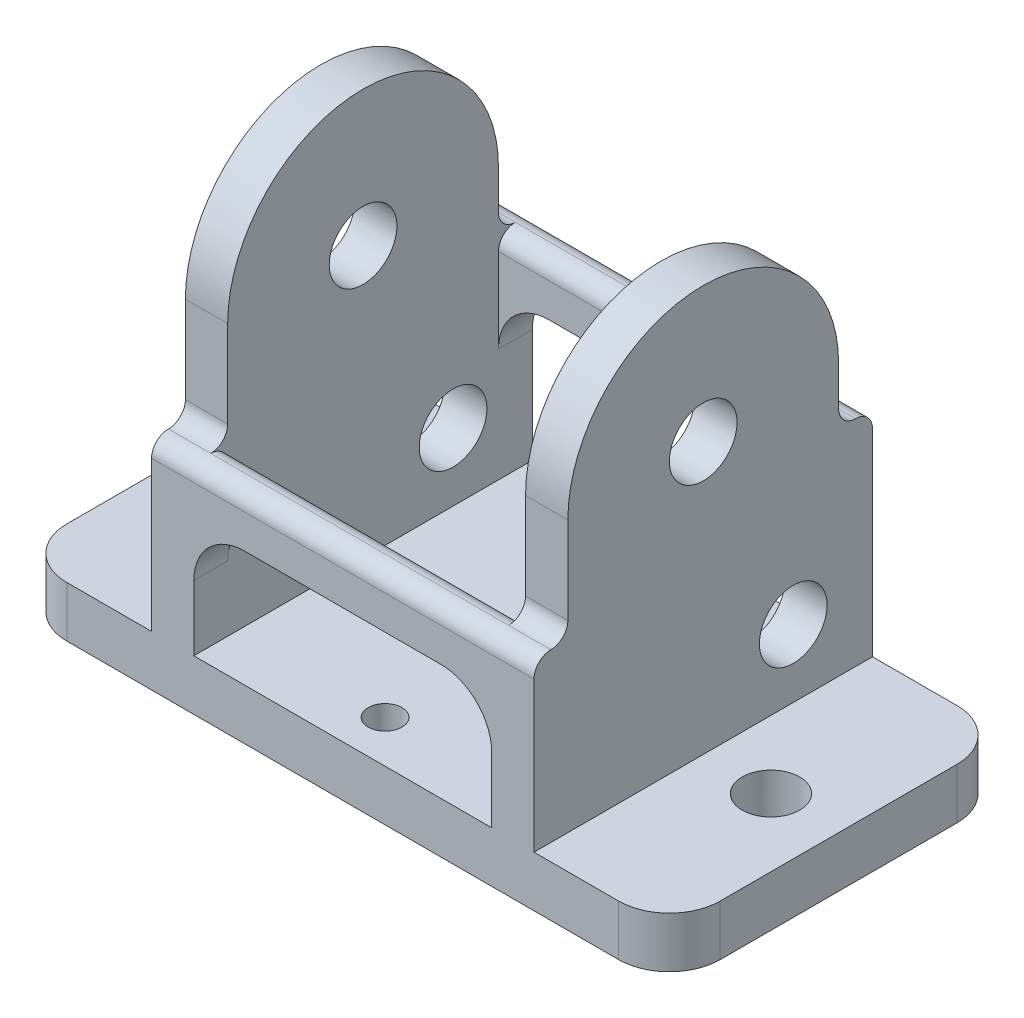
SolidWorks part; units mm, degrees
ref_plane "Plan de face" through (0, 0, 0) normal (0, 0, 1) x (1, 0, 0)
ref_plane "Plan de dessus" through (0, 0, 0) normal (0, 1, 0) x (1, 0, 0)
ref_plane "Plan de droite" through (0, 0, 0) normal (1, 0, 0) x (0, 0, -1)
sketch "Esquisse2" plane through (0, 0, 0) normal (0, 0, 1) x (1, 0, 0)
  line L0 (0, 1.475) -> (0, -1.8592) construction
  line L1 (-2.1467, 0) -> (3.7613, 0) construction
  line L4 (8.8, 2) -> (11.3, 2)
  line L5 (11.3, 2) -> (11.3, 8)
  line L6 (11.3, 8) -> (8.8, 8)
  line L7 (8.8, 8) -> (8.8, 2)
  dimension "D1" = 2.5
  dimension "D2" = 2
  dimension "D5" = 8
  dimension "D6" = 8.8
revolve "Révolution1" add sketch "Esquisse2" angle 360 about L1
sketch "Esquisse3" plane through (11.3, 0, 0) normal (1, 0, 0) x (0, 0, -1)
  line L1 (-10, -19) -> (10, -19)
  line L3 (-10, -16) -> (10, -16)
  line L4 (3.318, 0) -> (3.318, -16) construction
  line L5 (8, 0) -> (8, -6.3137)
  line L6 (5.6569, -5.6569) -> (12.7279, 1.4142) construction
  line L7 (0, -8) -> (10, -8) construction
  line L8 (8, -3.3137) -> (10, -3.3137)
  line L9 (10, -3.3137) -> (10, -19)
  line L10 (8, -6.3137) -> (10, -6.3137)
  line L11 (-5.6569, -5.6569) -> (-12.7279, 1.4142) construction
  line L12 (-8, -6.1421) -> (-10, -6.1421)
  line L13 (-12.7279, -1.4142) -> (-6.1421, -8) construction
  line L14 (-8, 0) -> (-8, -9.1421)
  line L15 (-8, -9.1421) -> (-10, -9.1421)
  line L16 (-10, -6.1421) -> (-10, -19)
  circle A0 centre (0, 0) radius 8 construction
  arc A1 (-8, 0) -> (8, 0) centre (0, 0) ccw
  circle A2 centre (0, 0) radius 3.318 construction
  circle A3 centre (5.318, -12) radius 2
  circle M5 centre (0, 0) radius 8
  dimension "D3" = 6.636
  dimension "D4" = 4
  dimension "D5" = 2
  dimension "D1" = 2
  dimension "D2" = 3
  dimension "D6" = 45
  dimension "D7" = 10
  dimension "D8" = 2
  dimension "D9" = 3
  dimension "D10" = 2
  dimension "D11" = 45
  dimension "D12" = 2
  dimension "D13" = 3
extrude "Boss.-Extru.1" add sketch "Esquisse3" against normal up to surface (2.5 mm away) contours L3 L1 | L3 M5 | L5 L10 L9 L8 | L12 L16 L15 L14 region at (11.3, -17.5, 0) region at (11.3, -11.0485, 0.0904) region at (11.3, -7.6421, 9) region at (11.3, -4.8137, -9) up to face at (8.8, 0, 2)
extrude "Boss.-Extru.2" add sketch "Esquisse3<3>" against normal up to surface (11.3 mm away) from surface contours L3 L1 | L5 L10 L9 L8 | L12 L16 L15 L14 region at (11.3, -17.5, 0) region at (11.3, -7.6421, 9) region at (11.3, -4.8137, -9) up to plane "Plan de droite" starting at face at (8.8, 0, 2)
sketch "Esquisse3<3>" plane through (11.3, 0, 0) normal (1, 0, 0) x (0, 0, -1) same geometry as "Esquisse3"
extrude "Boss-Extrude1" add sketch "Esquisse3<5>" along normal blind 8 contours L3 L16 L1 L9 region at (11.3, -17.5, 0)
sketch "Esquisse3<5>" plane through (11.3, 0, 0) normal (1, 0, 0) x (0, 0, -1) same geometry as "Esquisse3"
sketch "Sketch4" plane through (0, -16, 0) normal (0, 1, 0) x (1, 0, 0)
  line L0 (19.3, 10) -> (11.3, 10) construction
  circle A0 centre (15.3, 0) radius 1.7
  point P6 (15.3, 10)
  dimension "D1" = 3.4
extrude "Cut-Extrude1" cut sketch "Sketch4" against normal up to next
mirror "Symétrie1" about plane through (0, 0, 0) normal (1, 0, 0) of bodies 110 103
hole_wizard "Trous de centrage Ø2.0mm1" positions "Sketch1" profile "Sketch3" hole size "Ø2.0" standard "Ansi Metric" end condition up to next
sketch "Sketch1" plane through (0, -16, 0) normal (0, 1, 0) x (1, 0, 0)
  point P3 (0, -7.5)
  dimension "D1" = 7.5
sketch "Sketch3" plane through (0, -16, 7.5) normal (1, 0, 0) x (0, 0, 1)
  line L0 (0, 0) -> (0, 3)
  line L1 (0, 3) -> (1, 3)
  line L2 (1, 3) -> (1, 0)
  line L5 (1, 0) -> (0, 0)
  line L11 (0, -6.35) -> (0, 107.95) construction
  dimension "Thru Hole Dia." = 2
  dimension "Thru Hole Depth" = 3
fillet "Fillet1" radius 1 4 edges at (-10.05, -3.3137, -8) (10.05, -3.3137, -8) (-10.05, -6.1421, 8) (10.05, -6.1421, 8)
fillet "Fillet2" radius 1 4 edges at (0, -3.3137, -8) (0, -3.3137, -10) (0, -6.1421, 10) (0, -6.1421, 8)
fillet "Fillet3" radius 3 8 edges at (-8.8, -6.3137, -9) (8.8, -6.3137, -9) (8.8, -9.1421, 9) (-8.8, -9.1421, 9) (-19.3, -17.5, 10) (-19.3, -17.5, -10) (19.3, -17.5, -10) (19.3, -17.5, 10)
